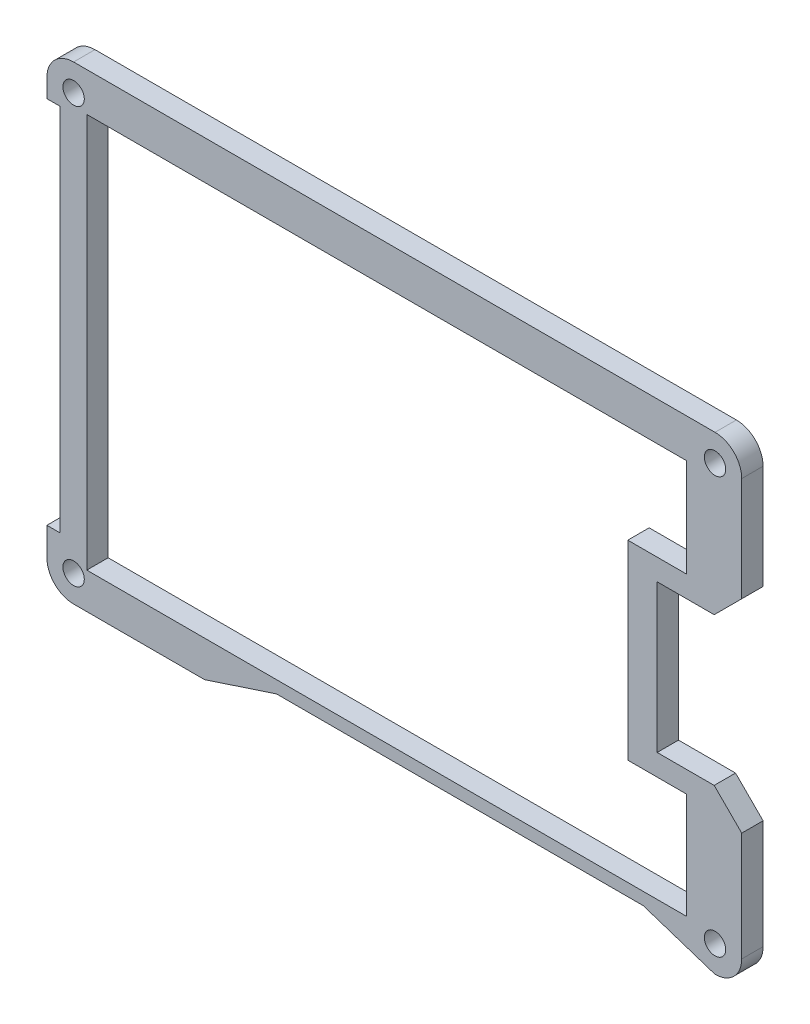
SolidWorks part; units mm, degrees
ref_plane "Front Plane" through (0, 0, 0) normal (0, 0, 1) x (1, 0, 0)
ref_plane "Top Plane" through (0, 0, 0) normal (0, 1, 0) x (1, 0, 0)
ref_plane "Right Plane" through (0, 0, 0) normal (1, 0, 0) x (0, 0, -1)
sketch "Sketch1" plane through (0, 0, 0) normal (0, 0, 1) x (1, 0, 0)
  line L0 (-309.8086, 128.8851) -> (-305.8779, 128.8851) construction
  line L1 (-305.8779, 128.8851) -> (-301.9473, 132.8157) construction
  line L2 (-301.9473, 132.8157) -> (-301.9473, 150.9704) construction
  line L3 (-305.7573, 154.7804) -> (-397.2471, 154.7804) construction
  line L4 (-401.0571, 150.9566) -> (-401.0571, 148.341) construction
  line L5 (-401.0571, 148.341) -> (-399.1521, 148.341) construction
  line L6 (-399.1521, 148.341) -> (-399.1521, 95.6449) construction
  line L7 (-399.1521, 95.6449) -> (-401.0571, 95.6449) construction
  line L8 (-401.0571, 95.6449) -> (-401.0571, 91.6593) construction
  line L9 (-378.5565, 87.8217) -> (-397.2472, 87.8217) construction
  line L10 (-368.3165, 91.1883) -> (-378.5565, 87.8217) construction
  line L11 (-315.9973, 91.1883) -> (-368.3165, 91.1883) construction
  line L12 (-315.9973, 91.1883) -> (-305.7573, 87.8217) construction
  line L13 (-301.9473, 91.6317) -> (-301.9473, 111.7465) construction
  line L14 (-305.8779, 115.6771) -> (-301.9473, 111.7465) construction
  line L15 (-309.8086, 115.6771) -> (-305.8779, 115.6771) construction
  line L16 (-309.8086, 128.8851) -> (-305.8779, 128.8851)
  line L17 (-305.8779, 128.8851) -> (-301.9473, 132.8157)
  line L18 (-301.9473, 132.8157) -> (-301.9473, 150.9704)
  line L19 (-305.7573, 154.7804) -> (-397.2471, 154.7804)
  line L20 (-401.0571, 150.9566) -> (-401.0571, 148.341)
  line L21 (-401.0571, 148.341) -> (-399.1521, 148.341)
  line L22 (-399.1521, 148.341) -> (-399.1521, 95.6449)
  line L23 (-399.1521, 95.6449) -> (-401.0571, 95.6449)
  line L24 (-401.0571, 95.6449) -> (-401.0571, 91.6593)
  line L25 (-378.5565, 87.8217) -> (-397.2472, 87.8217)
  line L26 (-368.3165, 91.1883) -> (-378.5565, 87.8217)
  line L27 (-315.9973, 91.1883) -> (-368.3165, 91.1883)
  line L28 (-315.9973, 91.1883) -> (-305.7573, 87.8217)
  line L29 (-301.9473, 91.6317) -> (-301.9473, 111.7465)
  line L30 (-305.8779, 115.6771) -> (-301.9473, 111.7465)
  line L31 (-309.8086, 115.6771) -> (-305.8779, 115.6771)
  line L32 (-309.8086, 128.8851) -> (-314.0123, 128.8851)
  line L33 (-314.0123, 128.8851) -> (-314.0123, 115.6771)
  line L34 (-314.0123, 115.6771) -> (-309.8086, 115.6771)
  line L35 (-395.3675, 92.9525) -> (-395.3675, 149.2432) construction
  line L36 (-395.3675, 92.9525) -> (-395.3675, 149.2432)
  line L37 (-395.3675, 149.2432) -> (-309.8086, 149.2432) construction
  line L38 (-395.3675, 149.2432) -> (-309.8086, 149.2432)
  line L39 (-395.3675, 92.9525) -> (-309.8086, 92.9525) construction
  line L40 (-395.3675, 92.9525) -> (-309.8086, 92.9525)
  line L41 (-309.8086, 111.7465) -> (-318.2033, 111.7465)
  line L42 (-309.8086, 115.6771) -> (-309.8086, 92.9525) construction
  line L43 (-318.2033, 111.7465) -> (-318.2033, 132.8157)
  line L44 (-318.2033, 134.8668) -> (-318.2033, 116.6297) construction
  line L45 (-318.2033, 132.8157) -> (-309.8086, 132.8157)
  line L46 (-309.8086, 149.2432) -> (-309.8086, 128.8851) construction
  line L47 (-309.8086, 132.8157) -> (-309.8086, 149.2432)
  line L48 (-309.8086, 111.7465) -> (-309.8086, 92.9525)
  arc A0 (-301.9473, 150.9704) -> (-305.7573, 154.7804) centre (-305.7573, 150.9704) ccw construction
  arc A1 (-397.2471, 154.7804) -> (-401.0571, 150.9566) centre (-397.2471, 150.9704) ccw construction
  arc A2 (-401.0571, 91.6593) -> (-397.2472, 87.8217) centre (-397.2472, 91.6317) ccw construction
  arc A3 (-305.7573, 87.8217) -> (-301.9473, 91.6317) centre (-305.7573, 91.6317) ccw construction
  arc A4 (-301.9473, 150.9704) -> (-305.7573, 154.7804) centre (-305.7573, 150.9704) ccw
  arc A5 (-397.2471, 154.7804) -> (-401.0571, 150.9566) centre (-397.2471, 150.9704) ccw
  arc A6 (-401.0571, 91.6593) -> (-397.2472, 87.8217) centre (-397.2472, 91.6317) ccw
  arc A7 (-305.7573, 87.8217) -> (-301.9473, 91.6317) centre (-305.7573, 91.6317) ccw
  dimension "D1" = 12.065
extrude "Boss-Extrude1" add sketch "Sketch1" along normal blind 3.048
sketch "Sketch2" plane through (0, 0, 0) normal (0, 0, -1) x (-1, 0, 0)
  circle A0 centre (305.7573, 150.9704) radius 1.3559
  circle A1 centre (397.2471, 150.9704) radius 1.3559
  circle A2 centre (397.2472, 91.6317) radius 1.3559
  circle A3 centre (305.7573, 91.6317) radius 1.3559
  dimension "D1" = 2.7118
extrude "Cut-Extrude1" cut sketch "Sketch2" against normal through all
sketch "Sketch3" plane through (0, 0, 0) normal (0, 0, -1) x (-1, 0, 0)
  circle A0 centre (305.7573, 150.9704) radius 1.524
  circle A1 centre (397.2471, 150.9704) radius 1.524
  circle A2 centre (397.2472, 91.6317) radius 1.524
  circle A3 centre (305.7573, 91.6317) radius 1.524
  dimension "D1" = 3.048
extrude "Cut-Extrude2" cut sketch "Sketch3" against normal through all
sketch "Sketch4" plane through (0, 0, 3.048) normal (0, 0, 1) x (1, 0, 0)
  line L0 (-301.9473, 136.1177) -> (-305.8779, 132.1871)
  line L1 (-301.9473, 132.8157) -> (-301.9473, 150.9704) construction
  line L2 (-305.8779, 132.1871) -> (-314.0123, 132.1871)
  line L3 (-314.0123, 111.1051) -> (-305.8779, 111.1051)
  line L4 (-305.8779, 111.1051) -> (-301.9473, 107.1745)
  line L5 (-301.9473, 91.6317) -> (-301.9473, 111.7465) construction
  line L6 (-314.0123, 132.1871) -> (-314.0123, 111.1051)
  line L7 (-301.9473, 136.1177) -> (-301.9473, 107.1745)
  line L8 (-305.8779, 128.8851) -> (-301.9473, 132.8157) construction
  line L9 (-301.9473, 111.7465) -> (-305.8779, 115.6771) construction
  line L10 (-314.0123, 128.8851) -> (-305.8779, 128.8851) construction
  line L11 (-305.8779, 115.6771) -> (-314.0123, 115.6771) construction
  line L12 (-314.0123, 115.6771) -> (-314.0123, 128.8851) construction
  line L13 (-301.9473, 139.1657) -> (-305.8779, 135.2351)
  line L14 (-305.8779, 135.2351) -> (-318.2033, 135.2351)
  line L15 (-318.2033, 135.2351) -> (-318.2033, 108.0571)
  line L16 (-318.2033, 108.0571) -> (-305.8779, 108.0571)
  line L17 (-305.8779, 108.0571) -> (-301.9473, 104.1265)
  line L18 (-301.9473, 104.1265) -> (-301.9473, 107.1745)
  line L19 (-318.2033, 111.7465) -> (-318.2033, 132.8157) construction
  line L20 (-301.9473, 139.1657) -> (-301.9473, 136.1177)
  line M5 (-314.0123, 128.8851) -> (-305.8779, 128.8851)
  line M6 (-305.8779, 128.8851) -> (-301.9473, 132.8157)
  line M7 (-301.9473, 132.8157) -> (-301.9473, 150.9704)
  line M22 (-301.9473, 91.6317) -> (-301.9473, 111.7465)
  line M23 (-301.9473, 111.7465) -> (-305.8779, 115.6771)
  line M24 (-305.8779, 115.6771) -> (-314.0123, 115.6771)
  line M25 (-314.0123, 115.6771) -> (-314.0123, 128.8851)
  line M26 (-309.8086, 111.7465) -> (-309.8086, 92.9525)
  line M30 (-309.8086, 149.2432) -> (-309.8086, 132.8157)
  line M31 (-309.8086, 132.8157) -> (-318.2033, 132.8157)
  line M33 (-318.2033, 111.7465) -> (-309.8086, 111.7465)
  dimension "D1" = 17.78
  dimension "D2" = 16.51
  dimension "D3" = 3.048
  dimension "D4" = 3.048
extrude "Cut-Extrude3" cut sketch "Sketch4" against normal through all contours L7 M6 M5 M25 M24 M23 | L2 L6 L0 M5 M6 M7 | L6 L3 L4 M24 M33 M26 M22 M23 region at (-307.9798, 131.1764, 3.048) region at (-307.5624, 122.2811, 3.048) region at (-307.7778, 112.8189, 3.048)
extrude "Boss-Extrude2" add sketch "Sketch4<4>" against normal up to vertex (3.048 mm away) contours L16 L17 L4 L3 M22 M26 | L15 L16 L3 L6 M26 M33 | L14 L15 M31 M30 region at (-305.878, 108.5984, 3.048) region at (-314.2058, 109.7565, 3.048) region at (-314.0059, 134.0254, 3.048) up to point (-318.2033, 132.8158, 0)
sketch "Sketch4<4>" plane through (0, 0, 3.048) normal (0, 0, 1) x (1, 0, 0) same geometry as "Sketch4"
